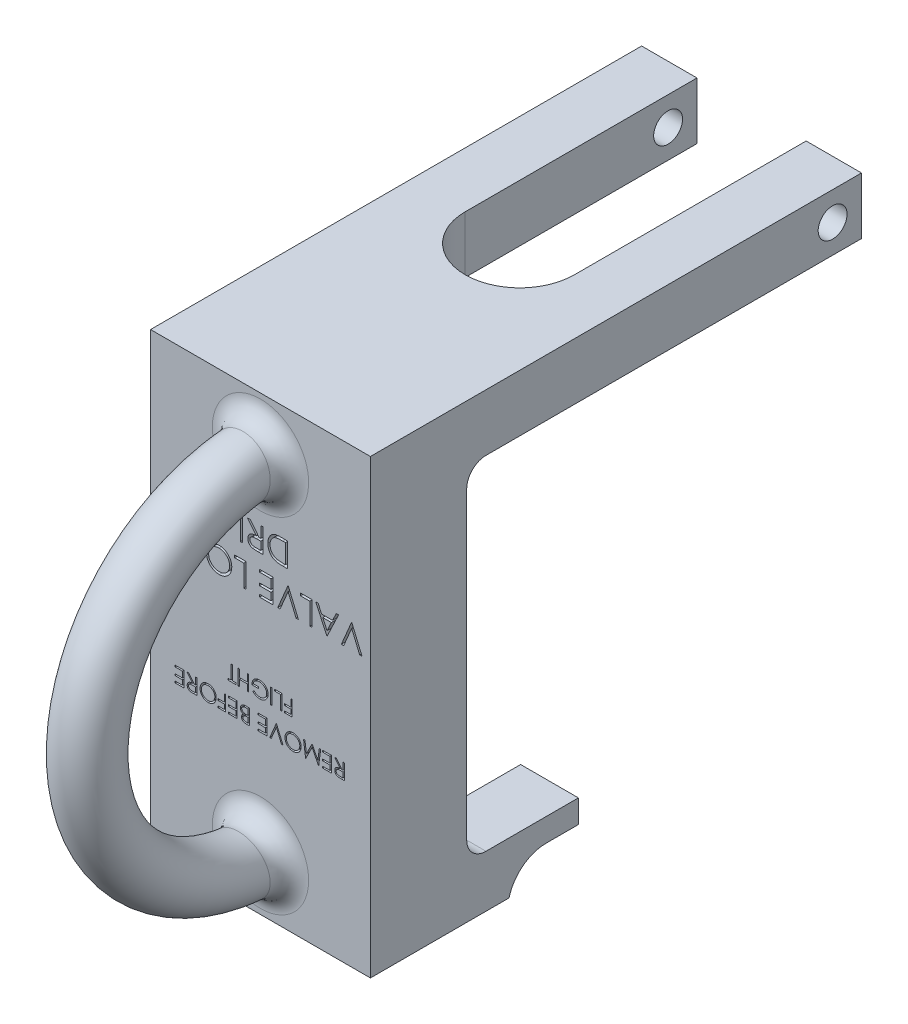
SolidWorks part; units mm, degrees
material "ABS PC"
ref_plane "Front Plane" through (0, 0, 0) normal (0, 0, 1) x (1, 0, 0)
ref_plane "Top Plane" through (0, 0, 0) normal (0, 1, 0) x (1, 0, 0)
ref_plane "Right Plane" through (0, 0, 0) normal (1, 0, 0) x (0, 0, -1)
sketch "Sketch1" plane through (0, 0, 0) normal (0, 0, 1) x (1, 0, 0)
  line L0 (0, 2.5) -> (0, -5) construction
  line L1 (-14.5, -5) -> (14.5, -5)
  line L2 (-14.5, -5) -> (-14.5, 2.5)
  line L3 (-14.5, 2.5) -> (14.5, 2.5)
  line L4 (14.5, -5) -> (14.5, 2.5)
  circle A0 centre (0, 0) radius 1.5
  dimension "D1" = 3
  dimension "D2" = 29
  dimension "D3" = 5
  dimension "D4" = 2.5
extrude "Boss-Extrude2" add sketch "Sketch1" along normal blind 21.59 contours L0 L3 L2 L1 A0 | L0 A0 | A0 L0 | L3 L0 A0 L1 L4 region at (7.4721, -1.292, 0) region at (-7.4721, -1.292, 0) region at (0.6366, 0, 0) region at (-0.6366, 0, 0)
ref_plane "Plane1" through (0, -1.25, 0) normal (0, 1, 0) x (1, 0, 0)
sketch "Sketch15" plane through (0, 2.5, 0) normal (0, 1, 0) x (1, 0, 0)
  line L0 (-14.5, 0) -> (14.5, 0) construction
  line L1 (-14.5, 0) -> (14.5, 0)
  line L3 (-14.5, 0) -> (14.5, 0)
  line L7 (-7.2, 12.61) -> (7.2, 12.61) construction
  line L10 (-14.5, 0) -> (-14.5, 43.18)
  line L11 (-14.5, 43.18) -> (-7.2, 43.18)
  line L12 (-7.2, 12.61) -> (-7.2, 43.18)
  line L14 (7.2, 12.61) -> (7.2, 43.18)
  line L15 (7.2, 43.18) -> (14.5, 43.18)
  line L16 (14.5, 0) -> (14.5, 43.18)
  arc A0 (-7.2, 12.61) -> (7.2, 12.61) centre (0, 12.61) ccw
  line M5 (14.5, 0) -> (-14.5, 0)
  dimension "D2" = 7.2
  dimension "D1" = 43.18
  dimension "D3" = 12.61
extrude "Boss-Extrude3" add sketch "Sketch15" against normal up to surface (7.5 mm away) contours A0 M5 region at (-13.9799, 2.5, -21.59) up to face at (0, -5, 10.795)
sketch "Sketch19" plane through (0, -5, 0) normal (0, 1, 0) x (1, 0, 0)
  line L0 (-6.88, -13.462) -> (6.88, -13.462)
  line L1 (-14.5, -21.59) -> (14.5, -21.59) construction
  line L2 (-6.88, -13.462) -> (-6.88, -8.89)
  line L3 (-6.88, -8.89) -> (-14.5, -8.89)
  line L4 (-14.5, -21.59) -> (-14.5, 43.18) construction
  line L5 (-14.5, -8.89) -> (-14.5, -21.59)
  line L6 (-14.5, -21.59) -> (14.5, -21.59)
  line L7 (14.5, -21.59) -> (14.5, -8.89)
  line L8 (14.5, -21.59) -> (14.5, 43.18) construction
  line L9 (14.5, -8.89) -> (6.88, -8.89)
  line L10 (6.88, -8.89) -> (6.88, -13.462)
  point P10 (0, -13.462)
  point P17 (0, -21.59)
  dimension "D1" = 8.128
  dimension "D2" = 7.62
  dimension "D3" = 12.7
extrude "Boss-Extrude4" add sketch "Sketch19" against normal blind 48.26
sketch "Sketch20" plane through (14.5, 0, 0) normal (1, 0, 0) x (0, 0, -1)
  line L0 (43.18, -5) -> (43.18, 2.5) construction
  circle A0 centre (39.37, -1.25) radius 1.905
  point P5 (43.18, -1.25)
  dimension "D2" = 3.81
  dimension "D1" = 3.81
extrude "Cut-Extrude1" cut sketch "Sketch20" against normal through all
fillet "Fillet1" radius 2.54 2 edges at (6.88, -29.13, 13.462) (-6.88, -29.13, 13.462)
fillet "Fillet2" radius 2.54 2 edges at (-10.69, -5, 8.89) (10.69, -5, 8.89)
fillet "Fillet3" radius 2.54 5 edges at (6.88, -5, 8.636) (6.1361, -5, 12.7181) (0, -5, 13.462) (-6.1361, -5, 12.7181) (-6.88, -5, 8.636)
sketch "Sketch21" plane through (0, 0, 8.89) normal (0, 0, -1) x (-1, 0, 0)
  line L0 (14.5, -53.26) -> (14.5, -7.54) construction
  line L1 (6.88, -53.26) -> (14.5, -53.26)
  line L2 (6.88, -53.26) -> (6.88, -50.212)
  line L3 (6.88, -50.212) -> (14.5, -50.212)
  line L4 (14.5, -53.26) -> (14.5, -50.212)
  line L5 (-14.5, -53.26) -> (-14.5, -7.54) construction
  line L6 (-6.88, -53.26) -> (-14.5, -53.26)
  line L7 (-6.88, -53.26) -> (-6.88, -50.212)
  line L8 (-6.88, -50.212) -> (-14.5, -50.212)
  line L9 (-14.5, -53.26) -> (-14.5, -50.212)
  dimension "D1" = 3.048
extrude "Boss-Extrude5" add sketch "Sketch21" along normal blind 14.732
fillet "Fillet4" radius 2.54 2 edges at (-10.69, -50.212, 8.89) (10.69, -50.212, 8.89)
sketch "Sketch29" plane through (0, 0, 21.59) normal (0, 0, 1) x (1, 0, 0)
  line L0 (14.5, -34.21) -> (-14.5, -34.21) construction
  line L1 (14.5, -53.26) -> (14.5, 2.5) construction
  line L2 (-14.5, -53.26) -> (-14.5, 2.5) construction
  line L3 (14.5, -17.7) -> (-14.5, -17.7) construction
  line L4 (14.5, -30.4) -> (-14.5, -30.4) construction
  line L5 (14.5, -12.62) -> (-14.5, -12.62) construction
  line L6 (-14.5, -53.26) -> (14.5, -53.26) construction
  text T0 "REMOVE BEFORE" font "Century Gothic" height 2.032
  text T1 "FLIGHT" font "Century Gothic" height 2.032
  text T2 "VALVE LOCK"
  text T3 "DRL"
  dimension "D1" = 3.81
  dimension "D2" = 19.05
  dimension "D3" = 12.7
  dimension "D4" = 5.08
extrude "Cut-Extrude2" cut sketch "Sketch29" against normal blind 2.54
sketch "Sketch30" plane through (0, -53.26, 0) normal (0, -1, 0) x (1, 0, 0)
  line L0 (-14.5, 3.302) -> (-6.88, 3.302)
  line L1 (6.88, 3.302) -> (14.5, 3.302)
  line L8 (-6.88, -5.842) -> (-6.88, 10.922)
  line L9 (-4.34, 13.462) -> (4.34, 13.462)
  line L10 (6.88, 10.922) -> (6.88, -5.842)
  line L11 (6.88, -5.842) -> (14.5, -5.842)
  line L12 (14.5, -5.842) -> (14.5, 21.59)
  line L13 (14.5, 21.59) -> (-14.5, 21.59)
  line L14 (-14.5, 21.59) -> (-14.5, -5.842)
  line L15 (-14.5, -5.842) -> (-6.88, -5.842)
  line L16 (-6.88, 3.302) -> (-6.88, 10.922)
  line L17 (-4.34, 13.462) -> (4.34, 13.462)
  line L18 (6.88, 10.922) -> (6.88, 3.302)
  line L20 (14.5, 3.302) -> (14.5, 21.59)
  line L21 (14.5, 21.59) -> (-14.5, 21.59)
  line L22 (-14.5, 21.59) -> (-14.5, 3.302)
  arc A2 (-4.34, 13.462) -> (-6.88, 10.922) centre (-4.34, 10.922) ccw
  arc A3 (6.88, 10.922) -> (4.34, 13.462) centre (4.34, 10.922) ccw
  arc A4 (-4.34, 13.462) -> (-6.88, 10.922) centre (-4.34, 10.922) ccw
  arc A5 (6.88, 10.922) -> (4.34, 13.462) centre (4.34, 10.922) ccw
  dimension "D2" = 18.288
  dimension "D1" = 0
extrude "Boss-Extrude6" add sketch "Sketch30" along normal blind 3.81
fillet "Fillet5" radius 5.08 2 edges at (10.69, -53.26, 3.302) (-10.69, -53.26, 3.302)
sketch "Sketch2" plane through (0, -25.38, 0) normal (1, 0, 0) x (0, -1, 0)
  line L1 (31.69, -21.59) -> (-27.88, -21.59) construction
  line L2 (31.69, -21.59) -> (-27.88, -21.59) construction
  arc A0 (-20.955, -21.59) -> (24.765, -21.59) centre (1.905, -21.59) ccw
  point P7 (0, 0)
  point P8 (0, 0)
  point P9 (0, 0)
  point P10 (0, 0)
  point P11 (0, 0)
  dimension "D1" = 22.86
sweep "Sweep1" add path "Sketch2" circular profile diameter 7.62 parameters "D3"=7.62
fillet "Fillet6" radius 2.54 2 edges at (3.81, -50.145, 21.59) (3.81, -4.425, 21.59)
